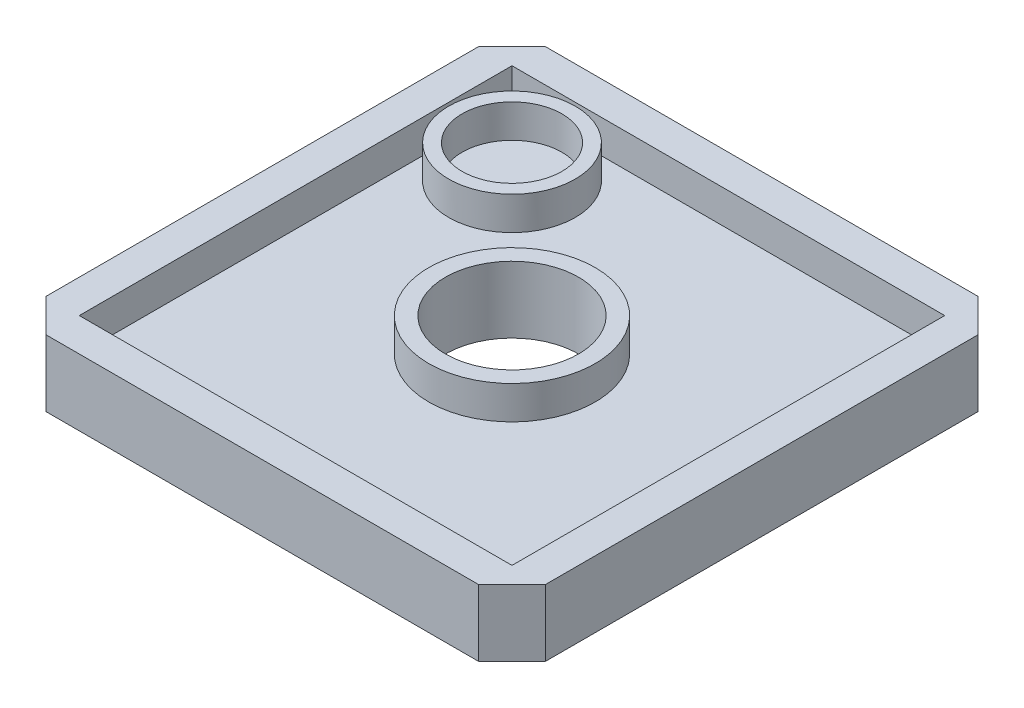
SolidWorks part; units mm, degrees
ref_plane "Front Plane" through (0, 0, 0) normal (0, 0, 1) x (1, 0, 0)
ref_plane "Top Plane" through (0, 0, 0) normal (0, 1, 0) x (1, 0, 0)
ref_plane "Right Plane" through (0, 0, 0) normal (1, 0, 0) x (0, 0, -1)
sketch "Sketch1" plane through (0, 0, 0) normal (0, 1, 0) x (1, 0, 0)
  line L0 (-65, 65) -> (65, 65)
  line L1 (-75, -75) -> (75, -75)
  line L2 (-75, -75) -> (-75, 75)
  line L3 (-75, 75) -> (75, 75)
  line L4 (75, -75) -> (75, 75)
  line L5 (-75, -75) -> (75, 75) construction
  line L6 (-75, 75) -> (75, -75) construction
  line L7 (65, -65) -> (65, 65)
  line L8 (-65, -65) -> (65, -65)
  line L9 (-65, -65) -> (-65, 65)
  point P0 (0, 0)
  dimension "D1" = 150
  dimension "D2" = 150
  dimension "D4" = 10
extrude "Boss-Extrude2" add sketch "Sketch1" along normal blind 20
extrude "Boss-Extrude3" add sketch "Sketch1<4>" along normal blind 10 contours L9 L8 L7 L0 region at (0, 0, 0)
sketch "Sketch1<4>" plane through (0, 0, 0) normal (0, 1, 0) x (1, 0, 0) same geometry as "Sketch1"
chamfer "Chamfer1" distance 10 4 edges at (75, 10, -75) (-75, 10, -75) (-75, 10, 75) (75, 10, 75)
sketch "Sketch2" plane through (0, 10, 0) normal (0, 1, 0) x (1, 0, 0)
  circle A0 centre (0, 0) radius 20
  dimension "D1" = 40
extrude "Cut-Extrude2" cut sketch "Sketch2" against normal blind 10
sketch "Sketch3" plane through (0, 10, 0) normal (0, 1, 0) x (1, 0, 0)
  circle A0 centre (0, 0) radius 25
  circle A1 centre (0, 0) radius 20
  circle M3 centre (0, 0) radius 20
  dimension "D1" = 50
extrude "Boss-Extrude4" add sketch "Sketch3" along normal blind 10 contours A0 M3 region at (-24.2929, 10, 0)
sketch "Sketch4" plane through (0, 10, 0) normal (0, 1, 0) x (1, 0, 0)
  line L0 (-65, -65) -> (-65, 65) construction
  line L1 (-65, 65) -> (65, 65) construction
  circle A0 centre (-45, 45) radius 15
  circle A1 centre (-45, 45) radius 19
  dimension "D1" = 30
  dimension "D2" = 20
  dimension "D3" = 20
  dimension "D4" = 4
extrude "Boss-Extrude5" add sketch "Sketch4" along normal up to surface (10 mm away) up to face at (0, 20, 0)
